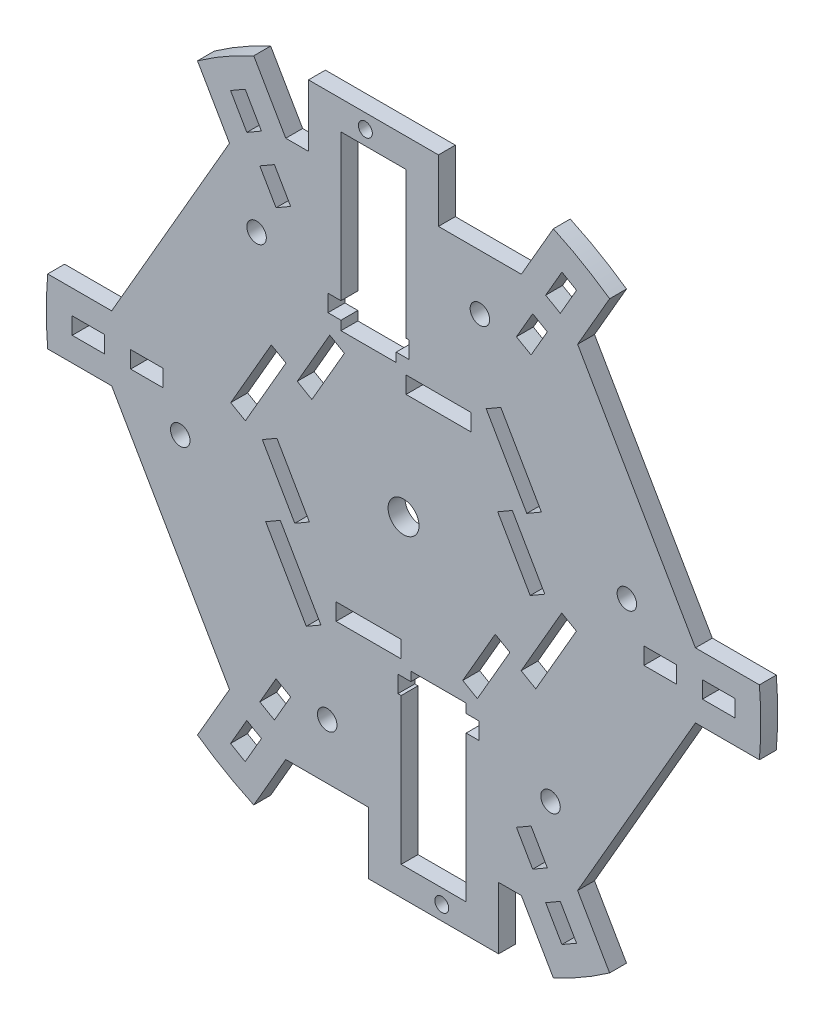
SolidWorks part; units mm, degrees
note: '?' marks a value the reader was unsure of.
ref_plane "Front Plane" through (0, 0, 0) normal (0, 0, 1) x (1, 0, 0)
ref_plane "Top Plane" through (0, 0, 0) normal (0, 1, 0) x (1, 0, 0)
ref_plane "Right Plane" through (0, 0, 0) normal (1, 0, 0) x (0, 0, -1)
sketch "Sketch1" plane through (0, 0, 0) normal (0, 0, 1) x (1, 0, 0)
  line L0 (-4.7625, 0) -> (-4.7625, 42.8001) construction
  line L1 (-4.7625, 40) -> (-2.2625, 40)
  line L2 (-2.2625, 40) -> (-2.2625, 48)
  line L3 (-2.2625, 48) -> (0.7375, 48)
  line L4 (0.7375, 48) -> (0.7375, 93)
  line L5 (0.7375, 93) -> (-19.2625, 93)
  line L6 (-19.2625, 93) -> (-19.2625, 40)
  line L7 (-19.2625, 40) -> (-16.7625, 40)
  line L8 (-16.7625, 40) -> (-4.7625, 40)
  line L9 (-4.7625, 40) -> (-4.7625, 0)
  line L10 (4.7625, -40) -> (2.2625, -40)
  line L11 (2.2625, -40) -> (2.2625, -48)
  line L12 (2.2625, -48) -> (-0.7375, -48)
  line L13 (-0.7375, -48) -> (-0.7375, -93)
  line L14 (-0.7375, -93) -> (19.2625, -93)
  line L15 (19.2625, -93) -> (19.2625, -40)
  line L16 (19.2625, -40) -> (16.7625, -40)
  line L17 (16.7625, -40) -> (4.7625, -40)
  line L18 (-2.2625, 40) -> (2.2625, -40) construction
  line L19 (37.0223, -15.8756) -> (35.7723, -18.0406) construction
  line L20 (35.7723, -18.0406) -> (42.7005, -22.0406) construction
  line L21 (42.7005, -22.0406) -> (41.2005, -24.6387) construction
  line L22 (41.2005, -24.6387) -> (80.1716, -47.1387) construction
  line L23 (80.1716, -47.1387) -> (90.1716, -29.8182) construction
  line L24 (90.1716, -29.8182) -> (44.2723, -3.3182) construction
  line L25 (44.2723, -3.3182) -> (43.0223, -5.4832) construction
  line L26 (43.0223, -5.4832) -> (37.0223, -15.8756) construction
  line L27 (0, 0) -> (2.2625, -40) construction
  line L28 (0, 0) -> (35.7723, -18.0406) construction
  line L29 (-37.0223, 15.8756) -> (-35.7723, 18.0406) construction
  line L30 (-35.7723, 18.0406) -> (-42.7005, 22.0406) construction
  line L31 (-42.7005, 22.0406) -> (-41.2005, 24.6387) construction
  line L32 (-41.2005, 24.6387) -> (-80.1716, 47.1387) construction
  line L33 (-80.1716, 47.1387) -> (-90.1716, 29.8182) construction
  line L34 (-90.1716, 29.8182) -> (-44.2723, 3.3182) construction
  line L35 (-44.2723, 3.3182) -> (-43.0223, 5.4832) construction
  line L36 (-43.0223, 5.4832) -> (-37.0223, 15.8756) construction
  line L37 (-35.7723, 18.0406) -> (0, 0) construction
  circle A0 centre (0, 0) radius 110
  circle A1 centre (0, 0) radius 4.7625
  point P14 (-4.7625, 0)
  point P27 (0, 0)
  point P46 (0, 0)
  dimension "D5" = 9.525
  dimension "D11" = 220
  dimension "D1" = 17
  dimension "D2" = 12
  dimension "D3" = 53
  dimension "D4" = 45
  dimension "D6" = 20
  dimension "D7" = 40
  dimension "D10" = 60
  dimension "D8" = 2
  dimension "D9" = 2
  dimension "D12" = 2
extrude "Boss-Extrude1" add sketch "Sketch1" along normal mid plane 5.2
sketch "Sketch2" plane through (0, 0, 2.6) normal (0, 0, 1) x (1, 0, 0)
  line L0 (-0.7375, -93) -> (19.2625, -93) construction
  line L1 (-10.7375, -82.8085) -> (-10.7375, -101.8725)
  line L2 (0, 0) -> (45.6639, 0) construction
  line L3 (29.2625, -101.8725) -> (29.2625, -82.8085)
  line L4 (-36.2625, -82.8085) -> (-10.7375, -82.8085)
  line L5 (-10.7375, -101.8725) -> (9.2625, -101.8725)
  line L6 (11.7625, -99.585) -> (11.7625, -101.8725) construction
  line L7 (9.2625, -101.8725) -> (29.2625, -101.8725)
  line L8 (29.2625, -82.8085) -> (36.2625, -82.8085)
  line L9 (9.2625, -93) -> (9.2625, -101.8725) construction
  line L12 (0, -53.2538) -> (0, -302.3208) construction
  line L13 (0, -2.86) -> (0, 2.86) construction
  line L14 (0, 0) -> (55, -95.2628) construction
  line L15 (0, 0) -> (-55, -95.2628) construction
  line L17 (19.2625, -93) -> (19.2625, -40) construction
  line L19 (-36.2625, -82.8085) -> (-46.112, -99.8683)
  line L24 (36.2625, -82.8085) -> (46.112, -99.8683)
  arc A0 (-46.112, -99.8683) -> (46.112, -99.8683) centre (0, 0) ccw
  circle A1 centre (0, 0) radius 110 construction
  circle A2 centre (0, 0) radius 110 construction
  circle A3 centre (11.7625, -97.435) radius 2.15
  point P4 (11.7625, -95.285)
  dimension "D10" = 4.3
  dimension "D2" = 2.2875
  dimension "D3" = 60
  dimension "D4" = 10
  dimension "D5" = 7
  dimension "D6" = 2.285
  dimension "D7" = 10
  dimension "D8" = 7.5
  dimension "D9" = 10
extrude "Cut-Extrude3" cut sketch "Sketch2" against normal through all
ref_axis "Axis1" through (0, 0, 1.7463) along (0, 0, -1)?
pattern_circular "CirPattern1" count 2 over 360 about axis through (0, 0, 0) along (0, 0, 1) of "Cut-Extrude3"
pattern_circular "CirPattern2" count 2 every 60 about axis through (0, 0, 0) along (0, 0, 1) of "CirPattern1", "Cut-Extrude3"
sketch "Sketch5" plane through (0, 0, 2.6) normal (0, 0, 1) x (1, 0, 0)
  line L0 (0, 0) -> (-174.8424, -100.9453) construction
  line L1 (0, 0) -> (-55, -95.2628) construction
  line L2 (0, 0) -> (-151.9227, 0) construction
  line L3 (89.8455, 10) -> (53.583, 72.8085)
  line L4 (63.4325, 89.8683) -> (53.583, 72.8085)
  line L5 (-89.8455, -10) -> (-53.583, -72.8085)
  line L6 (-36.2625, -82.8085) -> (-46.112, -99.8683) construction
  line L7 (109.5445, 10) -> (89.8455, 10)
  line L9 (-109.5445, 10) -> (-89.8455, 10) construction
  line L12 (-63.4325, -89.8683) -> (-53.583, -72.8085)
  line L13 (-109.5445, -10) -> (-89.8455, -10)
  arc A0 (-109.5445, -10) -> (-63.4325, -89.8683) centre (0, 0) ccw
  arc A1 (-109.5445, 10) -> (-46.112, -99.8683) centre (0, 0) ccw construction
  arc A2 (109.5445, 10) -> (63.4325, 89.8683) centre (0, 0) ccw
  point P19 (0, 0)
  point P23 (0, 0)
  point P26 (0, 0)
  dimension "D1" = 10
  dimension "D2" = 2
extrude "Cut-Extrude5" cut sketch "Sketch5" against normal through all
sketch "Sketch11" plane through (0, 0, 2.6) normal (0, 0, 1) x (1, 0, 0)
  line L0 (-19.2625, 40) -> (-2.2625, 40) construction
  line L1 (-19.067, 33.025) -> (-38.134, 0) construction
  line L2 (-38.134, 0) -> (-19.067, -33.025) construction
  line L3 (-19.067, -33.025) -> (19.067, -33.025) construction
  line L4 (19.067, -33.025) -> (38.134, 0) construction
  line L5 (38.134, 0) -> (19.067, 33.025) construction
  line L6 (19.067, 33.025) -> (-19.067, 33.025) construction
  line L7 (-1.7375, -48) -> (23.2625, -48)
  line L8 (-1.7375, -42.8) -> (2.2625, -42.8)
  line L9 (-1.7375, -48) -> (-1.7375, -42.8)
  line L10 (2.2625, -42.8) -> (19.2625, -42.8)
  line L11 (23.2625, -42.8) -> (23.2625, -48)
  line L12 (2.2625, -48) -> (-0.7375, -48) construction
  line L13 (-42.438, -22.4953) -> (-29.938, -44.1459)
  line L14 (-20.7625, -33.025) -> (-16.7625, -33.025)
  line L15 (-16.7625, -33.025) -> (-4.7625, -33.025)
  line L16 (-20.7625, -38.225) -> (-20.7625, -33.025)
  line L17 (-20.7625, -38.225) -> (-0.7625, -38.225)
  line L18 (-4.7625, -33.025) -> (-0.7625, -33.025)
  line L19 (19.2625, -93) -> (19.2625, -40) construction
  line L20 (-0.7625, -33.025) -> (-0.7625, -38.225)
  line L21 (-42.438, -22.4953) -> (-37.9346, -19.8953)
  line L22 (-37.9346, -19.8953) -> (-25.4346, -41.5459)
  line L23 (-25.4346, -41.5459) -> (-29.938, -44.1459)
  line L24 (-38.9817, 1.4684) -> (-36.9817, -1.9957)
  line L25 (-36.9817, -1.9957) -> (-30.9817, -12.3881)
  line L26 (-43.4851, -1.1316) -> (-38.9817, 1.4684)
  line L27 (-43.4851, -1.1316) -> (-33.4851, -18.4522)
  line L28 (-38.134, 0) -> (-19.067, -33.025) construction
  line L29 (-40.7005, 25.5047) -> (-53.2005, 3.8541)
  line L30 (-40.7005, 25.5047) -> (-36.1971, 22.9047)
  line L31 (-36.1971, 22.9047) -> (-48.6971, 1.2541)
  line L32 (-48.6971, 1.2541) -> (-53.2005, 3.8541)
  line L33 (-30.9817, -12.3881) -> (-28.9817, -15.8522)
  line L34 (-28.9817, -15.8522) -> (-33.4851, -18.4522)
  line L35 (-18.2192, 34.4934) -> (-20.2192, 31.0293)
  line L36 (-20.2192, 31.0293) -> (-26.2192, 20.6369)
  line L37 (-19.067, 33.025) -> (-38.134, 0) construction
  line L38 (1.7375, 48) -> (-23.2625, 48)
  line L39 (1.7375, 48) -> (1.7375, 42.8)
  line L40 (1.7375, 42.8) -> (-23.2625, 42.8)
  line L41 (-23.2625, 42.8) -> (-23.2625, 48)
  line L42 (-22.7226, 37.0934) -> (-18.2192, 34.4934)
  line L43 (-22.7226, 37.0934) -> (-32.7226, 19.7728)
  line L44 (-26.2192, 20.6369) -> (-28.2192, 17.1728)
  line L45 (-28.2192, 17.1728) -> (-32.7226, 19.7728)
  line L46 (19.067, 33.025) -> (-19.067, 33.025) construction
  line L47 (42.438, 22.4953) -> (29.938, 44.1459)
  line L48 (42.438, 22.4953) -> (37.9346, 19.8953)
  line L49 (37.9346, 19.8953) -> (25.4346, 41.5459)
  line L50 (25.4346, 41.5459) -> (29.938, 44.1459)
  line L51 (20.7625, 33.025) -> (16.7625, 33.025)
  line L52 (16.7625, 33.025) -> (4.7625, 33.025)
  line L53 (20.7625, 38.225) -> (20.7625, 33.025)
  line L54 (20.7625, 38.225) -> (0.7625, 38.225)
  line L55 (38.134, 0) -> (19.067, 33.025) construction
  line L56 (40.7005, -25.5047) -> (53.2005, -3.8541)
  line L57 (40.7005, -25.5047) -> (36.1971, -22.9047)
  line L58 (36.1971, -22.9047) -> (48.6971, -1.2541)
  line L59 (48.6971, -1.2541) -> (53.2005, -3.8541)
  line L60 (4.7625, 33.025) -> (0.7625, 33.025)
  line L61 (0.7625, 33.025) -> (0.7625, 38.225)
  line L62 (38.9817, -1.4684) -> (36.9817, 1.9957)
  line L63 (36.9817, 1.9957) -> (30.9817, 12.3881)
  line L64 (19.067, -33.025) -> (38.134, 0) construction
  line L65 (19.2625, -42.8) -> (23.2625, -42.8)
  line L66 (2.2625, -40) -> (2.2625, -48) construction
  line L67 (-16.7625, 40) -> (-16.7625, 20.0418) construction
  line L68 (45.2418, -53.2558) -> (59.9643, -61.7558) construction
  line L69 (-19.2625, 93) -> (-19.2625, 40) construction
  line L70 (43.4851, 1.1316) -> (38.9817, -1.4684)
  line L71 (22.7226, -37.0934) -> (32.7226, -19.7728) [skipped]
  line L72 (43.4851, 1.1316) -> (33.4851, 18.4522) [skipped]
  line L73 (-43.4851, -1.1316) -> (-33.4851, -18.4522) [skipped]
  line L74 (-22.7226, 37.0934) -> (-32.7226, 19.7728) [skipped]
  line L75 (20.7625, 38.225) -> (0.7625, 38.225) [skipped]
  line L76 (43.4851, 1.1316) -> (33.4851, 18.4522)
  line L77 (30.9817, 12.3881) -> (28.9817, 15.8522)
  line L78 (28.9817, 15.8522) -> (33.4851, 18.4522)
  line L79 (18.2192, -34.4934) -> (20.2192, -31.0293)
  line L80 (20.2192, -31.0293) -> (26.2192, -20.6369)
  line L81 (22.7226, -37.0934) -> (18.2192, -34.4934)
  line L82 (22.7226, -37.0934) -> (32.7226, -19.7728)
  line L83 (26.2192, -20.6369) -> (28.2192, -17.1728)
  line L84 (28.2192, -17.1728) -> (32.7226, -19.7728)
  line L85 (66.3455, -50.7032) -> (53.583, -72.8085) construction
  line L86 (0, 0) -> (0, -48) construction
  circle A0 centre (0, 0) radius 33.025 construction
  circle A1 centre (45.2418, -53.2558) radius 3
  circle A2 centre (-23.5, -65.8085) radius 3
  circle A3 centre (-68.7418, -12.5526) radius 3
  circle A4 centre (-45.2418, 53.2558) radius 3
  circle A5 centre (23.5, 65.8085) radius 3
  circle A6 centre (68.7418, 12.5526) radius 3
  point P72 (0, 0)
  point P109 (0, 0)
  point P123 (0, 0)
  dimension "D1" = 66.05
  dimension "D11" = 6
  dimension "D2" = 25
  dimension "D3" = 17
  dimension "D4" = 5.2
  dimension "D5" = 4
  dimension "D6" = 20
  dimension "D7" = 6
  dimension "D8" = 2.5
  dimension "D10" = 6
  dimension "D12" = 6
extrude "Cut-Extrude24" cut sketch "Sketch11" against normal through all
sketch "Sketch12" plane through (0, 0, 2.6) normal (0, 0, 1) x (1, 0, 0)
  line L0 (-55, -95.2628) -> (-37, -64.0859) construction
  line L1 (-37, -64.0859) -> (-34.7483, -65.3859)
  line L2 (-34.7483, -65.3859) -> (-39.7483, -74.0461)
  line L3 (-39.7483, -74.0461) -> (-44.2517, -71.4461)
  line L4 (-44.2517, -71.4461) -> (-39.2517, -62.7859)
  line L5 (-39.2517, -62.7859) -> (-37, -64.0859)
  line L6 (-51, -88.3346) -> (-48.7483, -89.6346)
  line L7 (-48.7483, -89.6346) -> (-43.7483, -80.9743)
  line L8 (-43.7483, -80.9743) -> (-48.2517, -78.3743)
  line L9 (-48.2517, -78.3743) -> (-53.2517, -87.0346)
  line L10 (-53.2517, -87.0346) -> (-51, -88.3346)
  line L11 (-74, 0) -> (-74, -2.6)
  line L12 (-74, -2.6) -> (-84, -2.6)
  line L13 (-84, -2.6) -> (-84, 2.6)
  line L14 (-84, 2.6) -> (-74, 2.6)
  line L15 (-74, 2.6) -> (-74, 0)
  line L16 (-102, 0) -> (-102, -2.6)
  line L17 (-102, -2.6) -> (-92, -2.6)
  line L18 (-92, -2.6) -> (-92, 2.6)
  line L19 (-92, 2.6) -> (-102, 2.6)
  line L20 (-102, 2.6) -> (-102, 0)
  line L21 (-110, 0) -> (-74, 0) construction
  line L22 (-37, 64.0859) -> (-39.2517, 62.7859)
  line L23 (-39.2517, 62.7859) -> (-44.2517, 71.4461)
  line L24 (-44.2517, 71.4461) -> (-39.7483, 74.0461)
  line L25 (-39.7483, 74.0461) -> (-34.7483, 65.3859)
  line L26 (-34.7483, 65.3859) -> (-37, 64.0859)
  line L27 (-51, 88.3346) -> (-53.2517, 87.0346)
  line L28 (-53.2517, 87.0346) -> (-48.2517, 78.3743)
  line L29 (-48.2517, 78.3743) -> (-43.7483, 80.9743)
  line L30 (-43.7483, 80.9743) -> (-48.7483, 89.6346)
  line L31 (-48.7483, 89.6346) -> (-51, 88.3346)
  line L32 (-55, 95.2628) -> (-37, 64.0859) construction
  line L33 (37, 64.0859) -> (34.7483, 65.3859)
  line L34 (34.7483, 65.3859) -> (39.7483, 74.0461)
  line L35 (39.7483, 74.0461) -> (44.2517, 71.4461)
  line L36 (44.2517, 71.4461) -> (39.2517, 62.7859)
  line L37 (39.2517, 62.7859) -> (37, 64.0859)
  line L38 (51, 88.3346) -> (48.7483, 89.6346)
  line L39 (48.7483, 89.6346) -> (43.7483, 80.9743)
  line L40 (43.7483, 80.9743) -> (48.2517, 78.3743)
  line L41 (48.2517, 78.3743) -> (53.2517, 87.0346)
  line L42 (53.2517, 87.0346) -> (51, 88.3346)
  line L43 (55, 95.2628) -> (37, 64.0859) construction
  line L44 (74, 0) -> (74, 2.6)
  line L45 (74, 2.6) -> (84, 2.6)
  line L46 (84, 2.6) -> (84, -2.6)
  line L47 (84, -2.6) -> (74, -2.6)
  line L48 (74, -2.6) -> (74, 0)
  line L49 (102, 0) -> (102, 2.6)
  line L50 (102, 2.6) -> (92, 2.6)
  line L51 (92, 2.6) -> (92, -2.6)
  line L52 (92, -2.6) -> (102, -2.6)
  line L53 (102, -2.6) -> (102, 0)
  line L54 (110, 0) -> (74, 0) construction
  line L55 (37, -64.0859) -> (39.2517, -62.7859)
  line L56 (39.2517, -62.7859) -> (44.2517, -71.4461)
  line L57 (44.2517, -71.4461) -> (39.7483, -74.0461)
  line L58 (39.7483, -74.0461) -> (34.7483, -65.3859)
  line L59 (34.7483, -65.3859) -> (37, -64.0859)
  line L60 (51, -88.3346) -> (53.2517, -87.0346)
  line L61 (53.2517, -87.0346) -> (48.2517, -78.3743)
  line L62 (48.2517, -78.3743) -> (43.7483, -80.9743)
  line L63 (43.7483, -80.9743) -> (48.7483, -89.6346)
  line L64 (48.7483, -89.6346) -> (51, -88.3346)
  line L65 (55, -95.2628) -> (37, -64.0859) construction
  arc A1 (-63.4325, -89.8683) -> (-46.112, -99.8683) centre (0, 0) ccw construction
  point P73 (0, 0)
  dimension "D1" = 8
  dimension "D2" = 10
  dimension "D3" = 8
  dimension "D4" = 5.2
  dimension "D5" = 6
extrude "Cut-Extrude25" cut sketch "Sketch12" against normal through all
sketch "Sketch13" plane through (0, 0, 2.6) normal (0, 0, 1) x (1, 0, 0)
  line L0 (-86.3455, 16.0622) -> (-66.3455, 50.7032)
  line L1 (-66.3455, 50.7032) -> (-76.3455, 67.5957)
  line L2 (-76.3455, 67.5957) -> (-92.5607, 57.9967)
  line L3 (-92.5607, 57.9967) -> (-113.3044, 22.0676)
  line L4 (-113.3044, 22.0676) -> (-86.3455, 16.0622)
  line L5 (66.3455, -50.7032) -> (83.1054, -79.0149)
  line L6 (83.1054, -79.0149) -> (116.5395, -32.2591)
  line L7 (116.5395, -32.2591) -> (108.0454, -17.9104)
  line L8 (108.0454, -17.9104) -> (86.3455, -16.0622)
  line L9 (86.3455, -16.0622) -> (66.3455, -50.7032)
extrude "Cut-Extrude26" cut sketch "Sketch13" against normal through all
ref_plane "Plane2" through (0, 0, 0) normal (0.866, 0.5, 0) x (0, 0, -1)
